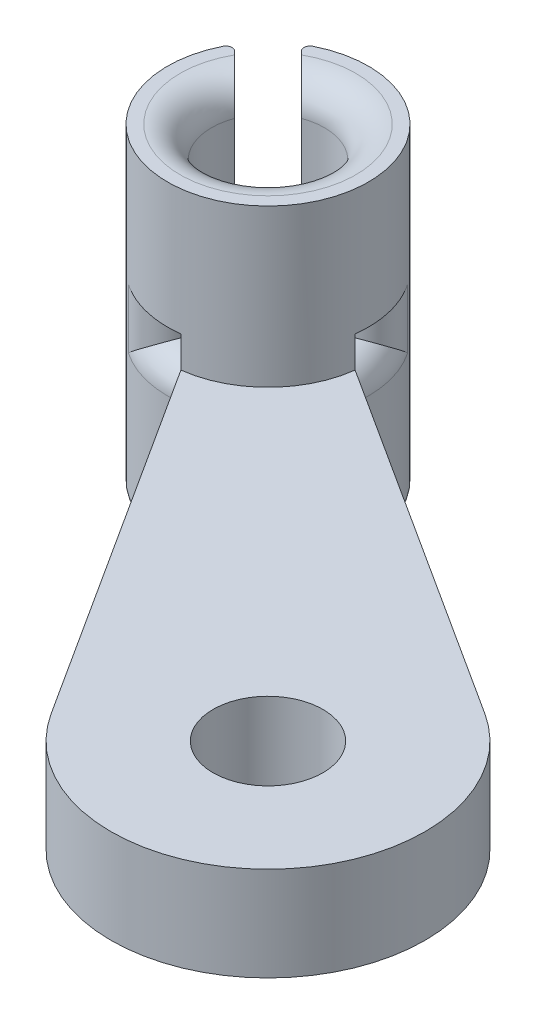
SolidWorks part; units mm, degrees
ref_plane "Front Plane" through (0, 0, 0) normal (0, 0, 1) x (1, 0, 0)
ref_plane "Top Plane" through (0, 0, 0) normal (0, 1, 0) x (1, 0, 0)
ref_plane "Right Plane" through (0, 0, 0) normal (1, 0, 0) x (0, 0, -1)
sketch "Sketch1" plane through (0, 0, 0) normal (0, 1, 0) x (1, 0, 0)
  circle A0 centre (0, 0) radius 1.7
  circle A1 centre (0, 0) radius 3.2
  dimension "D1" = 3.4
  dimension "D2" = 1.5
extrude "Boss-Extrude1" add sketch "Sketch1" along normal blind 5
sketch "Sketch2" plane through (0, 5, 0) normal (0, 1, 0) x (1, 0, 0)
  line L0 (-3.1749, 0.4) -> (-1.755, 0.4)
  line L1 (-3.1749, -0.4) -> (-1.755, -0.4)
  line L2 (0, 0) -> (-4.4135, 0) construction
  line L3 (0.4, 3.1749) -> (0.4, 1.755)
  line L4 (-0.4, 3.1749) -> (-0.4, 1.755)
  line L5 (3.1749, -0.4) -> (1.755, -0.4)
  line L6 (3.1749, 0.4) -> (1.755, 0.4)
  line L7 (-0.4, -3.1749) -> (-0.4, -1.755)
  line L8 (0.4, -3.1749) -> (0.4, -1.755)
  arc A0 (-0.4, 1.755) -> (-1.755, 0.4) centre (0, 0) ccw
  arc A1 (-0.4, 3.1749) -> (-3.1749, 0.4) centre (0, 0) ccw
  circle A2 centre (0, 0) radius 3.2 construction
  circle A3 centre (0, 0) radius 1.8
  arc A4 (-1.755, -0.4) -> (1.755, -0.4) centre (0, 0) ccw
  arc A5 (-3.1749, -0.4) -> (3.1749, -0.4) centre (0, 0) ccw
  arc A6 (3.1749, 0.4) -> (0.4, 3.1749) centre (0, 0) ccw
  arc A7 (1.755, 0.4) -> (0.4, 1.755) centre (0, 0) ccw
  point P22 (0, 0)
  circle M7 centre (0, 0) radius 3.2
  dimension "D2" = 0.4
  dimension "D3" = 0.4
  dimension "D1" = 0.1
  dimension "D4" = 4
extrude "Boss-Extrude2" add sketch "Sketch2" along normal blind 1 contours A0 L4 L0 M7 | A4 L1 L7 M7 | A7 L6 L3 M7 | A4 L8 L5 M7 region at (-1.7075, 5, -1.7075) region at (-1.7075, 5, 1.7075) region at (1.7075, 5, -1.7075) region at (1.7075, 5, 1.7075)
sketch "Sketch3" plane through (0, 6, 0) normal (0, 1, 0) x (1, 0, 0)
  circle A0 centre (0, 0) radius 1.8
  circle A2 centre (0, 0) radius 3.2
extrude "Boss-Extrude3" add sketch "Sketch3" along normal blind 4 contours A2 | A0
sketch "Sketch4" plane through (0, 10, 0) normal (0, 1, 0) x (1, 0, 0)
  line L0 (-2.73, 1.6694) -> (-1.6091, 0.5484)
  line L1 (-1.6694, 2.73) -> (-0.5484, 1.6091)
  line L2 (0, 0) -> (-2.2627, 2.2627) construction
  line L11 (0.4, 1.755) -> (0.4, 3.1749)
  line L12 (0.4, 1.755) -> (0.4, 3.1749)
  line L13 (-0.4, 3.1749) -> (-0.4, 1.755)
  line L14 (-0.4, 3.1749) -> (-0.4, 1.755)
  line L21 (-1.755, 0.4) -> (-3.1749, 0.4)
  line L22 (-1.755, 0.4) -> (-3.1749, 0.4)
  line L23 (-3.1749, -0.4) -> (-1.755, -0.4)
  line L24 (-3.1749, -0.4) -> (-1.755, -0.4)
  line L25 (1.755, -0.4) -> (3.1749, -0.4)
  line L26 (1.755, -0.4) -> (3.1749, -0.4)
  line L27 (3.1749, 0.4) -> (1.755, 0.4)
  line L28 (3.1749, 0.4) -> (1.755, 0.4)
  line L29 (0.4, -3.1749) -> (0.4, -1.755)
  line L30 (0.4, -3.1749) -> (0.4, -1.755)
  line L31 (-0.4, -1.755) -> (-0.4, -3.1749)
  line L32 (-0.4, -1.755) -> (-0.4, -3.1749)
  circle A0 centre (0, 0) radius 3.2 construction
  circle A1 centre (0, 0) radius 1.7 construction
  circle A2 centre (0, 0) radius 1.7
  circle A3 centre (0, 0) radius 3.2 construction
  circle A5 centre (0, 0) radius 3.2
  arc A9 (0.4, 3.1749) -> (-0.4, 3.1749) centre (0, 0) ccw
  arc A15 (0.4, 3.1749) -> (-0.4, 3.1749) centre (0, 0) ccw
  arc A20 (1.755, 0.4) -> (0.4, 1.755) centre (0, 0) ccw
  arc A21 (1.755, 0.4) -> (0.4, 1.755) centre (0, 0) ccw
  arc A22 (-0.4, 1.755) -> (-1.755, 0.4) centre (0, 0) ccw
  arc A23 (-0.4, 1.755) -> (-1.755, 0.4) centre (0, 0) ccw
  arc A24 (-3.1749, 0.4) -> (-3.1749, -0.4) centre (0, 0) ccw
  arc A25 (-3.1749, 0.4) -> (-3.1749, -0.4) centre (0, 0) ccw
  arc A26 (-1.755, -0.4) -> (-0.4, -1.755) centre (0, 0) ccw
  arc A27 (-1.755, -0.4) -> (-0.4, -1.755) centre (0, 0) ccw
  arc A28 (3.1749, -0.4) -> (3.1749, 0.4) centre (0, 0) ccw
  arc A29 (3.1749, -0.4) -> (3.1749, 0.4) centre (0, 0) ccw
  arc A30 (0.4, -1.755) -> (1.755, -0.4) centre (0, 0) ccw
  arc A31 (0.4, -1.755) -> (1.755, -0.4) centre (0, 0) ccw
  arc A32 (-0.4, -3.1749) -> (0.4, -3.1749) centre (0, 0) ccw
  arc A33 (-0.4, -3.1749) -> (0.4, -3.1749) centre (0, 0) ccw
  dimension "D2" = 0.75
  dimension "D3" = 0.75
  dimension "D1" = 0
extrude "Cut-Extrude1" cut sketch "Sketch4" against normal through all contours L2 L0 | A2 L2 L0 | L2 A2 L1 A23 | L2 A23 L1 region at (-2.0054, 10, -1.4705) region at (-1.4669, 10, -0.9277) region at (-1.4705, 10, -2.0054) region at (-0.9277, 10, -1.4669)
sketch "Sketch5" plane through (0, 5, 0) normal (0, 1, 0) x (1, 0, 0)
  line L0 (0, 0) -> (12.0208, -12.0208) construction
  line L1 (3.1749, -0.4) -> (14.7221, -7.8133)
  line L2 (0.4, -3.1749) -> (7.8133, -14.7221)
  line L9 (-1.6091, 0.5484) -> (-1.6874, 0.6267)
  line L15 (-1.755, 0.4) -> (-3.1749, 0.4)
  line L16 (-0.6267, 1.6874) -> (-0.5484, 1.6091)
  line L17 (-1.6091, 0.5484) -> (-1.6874, 0.6267)
  line L24 (-0.6267, 1.6874) -> (-0.5484, 1.6091)
  line L25 (-1.755, 0.4) -> (-3.1749, 0.4)
  line L26 (-3.1749, -0.4) -> (-1.755, -0.4)
  line L27 (-3.1749, -0.4) -> (-1.755, -0.4)
  line L28 (1.755, -0.4) -> (3.1749, -0.4)
  line L29 (1.755, -0.4) -> (3.1749, -0.4)
  line L30 (3.1749, 0.4) -> (1.755, 0.4)
  line L31 (3.1749, 0.4) -> (1.755, 0.4)
  line L32 (0.4, 1.755) -> (0.4, 3.1749)
  line L33 (0.4, 1.755) -> (0.4, 3.1749)
  line L34 (-0.4, 3.1749) -> (-0.4, 1.755)
  line L35 (-0.4, 3.1749) -> (-0.4, 1.755)
  line L36 (-0.4, -1.755) -> (-0.4, -3.1749)
  line L37 (-0.4, -1.755) -> (-0.4, -3.1749)
  line L38 (0.4, -3.1749) -> (0.4, -1.755)
  line L39 (0.4, -3.1749) -> (0.4, -1.755)
  circle A0 centre (12.0208, -12.0208) radius 1.75
  arc A1 (7.8133, -14.7221) -> (14.7221, -7.8133) centre (12.0208, -12.0208) ccw
  arc A3 (-2.73, 1.6694) -> (-1.6694, 2.73) centre (0, 0) ccw construction
  arc A4 (-2.73, 1.6694) -> (-1.6694, 2.73) centre (0, 0) ccw
  arc A11 (-3.1749, 0.4) -> (-3.1749, -0.4) centre (0, 0) ccw
  arc A15 (-1.6874, 0.6267) -> (-1.755, 0.4) centre (0, 0) ccw
  arc A17 (-1.6091, 0.5484) -> (-0.5484, 1.6091) centre (0, 0) ccw
  arc A19 (-3.1749, 0.4) -> (-3.1749, -0.4) centre (0, 0) ccw
  arc A25 (-1.6091, 0.5484) -> (-0.5484, 1.6091) centre (0, 0) ccw
  arc A26 (-1.755, -0.4) -> (-0.4, -1.755) centre (0, 0) ccw
  arc A27 (-1.755, -0.4) -> (-0.4, -1.755) centre (0, 0) ccw
  arc A28 (3.1749, -0.4) -> (3.1749, 0.4) centre (0, 0) ccw
  arc A29 (3.1749, -0.4) -> (3.1749, 0.4) centre (0, 0) ccw
  arc A30 (1.755, 0.4) -> (0.4, 1.755) centre (0, 0) ccw
  arc A31 (1.755, 0.4) -> (0.4, 1.755) centre (0, 0) ccw
  arc A32 (0.4, 3.1749) -> (-0.4, 3.1749) centre (0, 0) ccw
  arc A33 (0.4, 3.1749) -> (-0.4, 3.1749) centre (0, 0) ccw
  arc A34 (-0.4, -3.1749) -> (0.4, -3.1749) centre (0, 0) ccw
  arc A35 (-0.4, -3.1749) -> (0.4, -3.1749) centre (0, 0) ccw
  arc A36 (0.4, -1.755) -> (1.755, -0.4) centre (0, 0) ccw
  arc A37 (0.4, -1.755) -> (1.755, -0.4) centre (0, 0) ccw
  arc A38 (-1.6874, 0.6267) -> (-1.755, 0.4) centre (0, 0) ccw
  arc A40 (-0.4, 1.755) -> (-0.6267, 1.6874) centre (0, 0) ccw
  arc A41 (-0.4, 1.755) -> (-0.6267, 1.6874) centre (0, 0) ccw
  point P14 (0, 0)
  point P20 (16.9497, -1.3067)
  point P21 (12.8371, -11.1449)
  point P22 (0, 0)
  point P26 (0, 0)
  dimension "D2" = 3.5
  dimension "D3" = 10
  dimension "D1" = 17
  dimension "D4" = 0
extrude "Boss-Extrude4" add sketch "Sketch5" against normal blind 3 contours L2 A1 L1 A0 region at (9.1845, 5, 9.1845)
fillet "Fillet1" radius 0.2 2 edges at (-2.73, 5, -1.6694) (-1.6694, 5, -2.73)
fillet "Fillet2" radius 0.9 8 edges at (3.2, 5, 0) (-3.1749, 5.5, 0.4) (-3.2, 5, 0) (0, 5, -3.2) (-0.4, 5.5, 3.1749) (0, 5, 3.2) (3.1749, 5.5, -0.4) (0.4, 5.5, -3.1749)
fillet "Fillet3" radius 1 2 edges at (1.2021, 0, 1.2021) (1.2728, 10, 1.2728)
fillet "Fillet4" radius 0.2 9 edges at (-0.5484, 3, -1.6091) (-0.8173, 0.2417, -1.8779) (-1.3928, 0, -2.4534) (-1.5378, 0, -2.716) (2.2627, 0, 2.2627) (-2.716, 0, -1.5378) (-2.4534, 0, -1.3928) (-1.7555, 0.4164, -0.6948) (-1.6091, 3, -0.5484)
